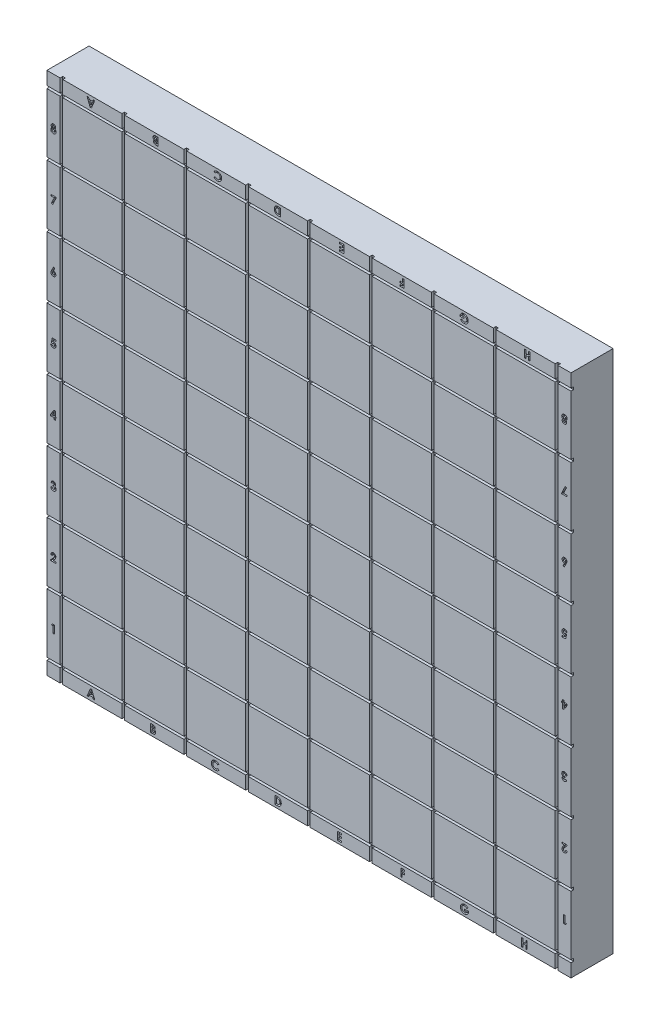
SolidWorks part; units mm, degrees
ref_plane "Płaszczyzna przednia" through (0, 0, 0) normal (0, 0, 1) x (1, 0, 0)
ref_plane "Płaszczyzna górna" through (0, 0, 0) normal (0, 1, 0) x (1, 0, 0)
ref_plane "Płaszczyzna prawa" through (0, 0, 0) normal (1, 0, 0) x (0, 0, -1)
sketch "Szkic3" plane through (0, 0, 0) normal (0, 0, 1) x (1, 0, 0)
  line L0 (247.5956, 2770.7602) -> (247.5956, 2725.7602)
  line L1 (200.5956, 2770.7602) -> (245.5956, 2770.7602)
  line L2 (200.5956, 2770.7602) -> (200.5956, 2725.7602)
  line L3 (200.5956, 2725.7602) -> (245.5956, 2725.7602)
  line L4 (245.5956, 2770.7602) -> (245.5956, 2725.7602)
  line L5 (247.5956, 2770.7602) -> (292.5956, 2770.7602)
  line L6 (292.5956, 2770.7602) -> (292.5956, 2725.7602)
  line L7 (247.5956, 2725.7602) -> (292.5956, 2725.7602)
  line L8 (294.5956, 2770.7602) -> (294.5956, 2725.7602)
  line L9 (294.5956, 2770.7602) -> (339.5956, 2770.7602)
  line L10 (339.5956, 2770.7602) -> (339.5956, 2725.7602)
  line L11 (294.5956, 2725.7602) -> (339.5956, 2725.7602)
  line L12 (341.5956, 2770.7602) -> (341.5956, 2725.7602)
  line L13 (341.5956, 2770.7602) -> (386.5956, 2770.7602)
  line L14 (386.5956, 2770.7602) -> (386.5956, 2725.7602)
  line L15 (341.5956, 2725.7602) -> (386.5956, 2725.7602)
  line L16 (388.5956, 2770.7602) -> (388.5956, 2725.7602)
  line L17 (388.5956, 2770.7602) -> (433.5956, 2770.7602)
  line L18 (433.5956, 2770.7602) -> (433.5956, 2725.7602)
  line L19 (388.5956, 2725.7602) -> (433.5956, 2725.7602)
  line L20 (435.5956, 2770.7602) -> (435.5956, 2725.7602)
  line L21 (435.5956, 2770.7602) -> (480.5956, 2770.7602)
  line L22 (480.5956, 2770.7602) -> (480.5956, 2725.7602)
  line L23 (435.5956, 2725.7602) -> (480.5956, 2725.7602)
  line L24 (482.5956, 2770.7602) -> (482.5956, 2725.7602)
  line L25 (482.5956, 2770.7602) -> (527.5956, 2770.7602)
  line L26 (527.5956, 2770.7602) -> (527.5956, 2725.7602)
  line L27 (482.5956, 2725.7602) -> (527.5956, 2725.7602)
  line L28 (529.5956, 2770.7602) -> (529.5956, 2725.7602)
  line L29 (529.5956, 2770.7602) -> (574.5956, 2770.7602)
  line L30 (574.5956, 2770.7602) -> (574.5956, 2725.7602)
  line L31 (529.5956, 2725.7602) -> (574.5956, 2725.7602)
  line L32 (247.5956, 2723.7602) -> (247.5956, 2678.7602)
  line L33 (247.5956, 2723.7602) -> (292.5956, 2723.7602)
  line L34 (292.5956, 2723.7602) -> (292.5956, 2678.7602)
  line L35 (247.5956, 2678.7602) -> (292.5956, 2678.7602)
  line L36 (294.5956, 2723.7602) -> (294.5956, 2678.7602)
  line L37 (294.5956, 2723.7602) -> (339.5956, 2723.7602)
  line L38 (339.5956, 2723.7602) -> (339.5956, 2678.7602)
  line L39 (294.5956, 2678.7602) -> (339.5956, 2678.7602)
  line L40 (341.5956, 2723.7602) -> (341.5956, 2678.7602)
  line L41 (341.5956, 2723.7602) -> (386.5956, 2723.7602)
  line L42 (386.5956, 2723.7602) -> (386.5956, 2678.7602)
  line L43 (341.5956, 2678.7602) -> (386.5956, 2678.7602)
  line L44 (388.5956, 2723.7602) -> (388.5956, 2678.7602)
  line L45 (388.5956, 2723.7602) -> (433.5956, 2723.7602)
  line L46 (433.5956, 2723.7602) -> (433.5956, 2678.7602)
  line L47 (388.5956, 2678.7602) -> (433.5956, 2678.7602)
  line L48 (435.5956, 2723.7602) -> (435.5956, 2678.7602)
  line L49 (435.5956, 2723.7602) -> (480.5956, 2723.7602)
  line L50 (480.5956, 2723.7602) -> (480.5956, 2678.7602)
  line L51 (435.5956, 2678.7602) -> (480.5956, 2678.7602)
  line L52 (482.5956, 2723.7602) -> (482.5956, 2678.7602)
  line L53 (482.5956, 2723.7602) -> (527.5956, 2723.7602)
  line L54 (527.5956, 2723.7602) -> (527.5956, 2678.7602)
  line L55 (482.5956, 2678.7602) -> (527.5956, 2678.7602)
  line L56 (529.5956, 2723.7602) -> (529.5956, 2678.7602)
  line L57 (529.5956, 2723.7602) -> (574.5956, 2723.7602)
  line L58 (574.5956, 2723.7602) -> (574.5956, 2678.7602)
  line L59 (529.5956, 2678.7602) -> (574.5956, 2678.7602)
  line L60 (247.5956, 2676.7602) -> (247.5956, 2631.7602)
  line L61 (247.5956, 2676.7602) -> (292.5956, 2676.7602)
  line L62 (292.5956, 2676.7602) -> (292.5956, 2631.7602)
  line L63 (247.5956, 2631.7602) -> (292.5956, 2631.7602)
  line L64 (294.5956, 2676.7602) -> (294.5956, 2631.7602)
  line L65 (294.5956, 2676.7602) -> (339.5956, 2676.7602)
  line L66 (339.5956, 2676.7602) -> (339.5956, 2631.7602)
  line L67 (294.5956, 2631.7602) -> (339.5956, 2631.7602)
  line L68 (341.5956, 2676.7602) -> (341.5956, 2631.7602)
  line L69 (341.5956, 2676.7602) -> (386.5956, 2676.7602)
  line L70 (386.5956, 2676.7602) -> (386.5956, 2631.7602)
  line L71 (341.5956, 2631.7602) -> (386.5956, 2631.7602)
  line L72 (388.5956, 2676.7602) -> (388.5956, 2631.7602)
  line L73 (388.5956, 2676.7602) -> (433.5956, 2676.7602)
  line L74 (433.5956, 2676.7602) -> (433.5956, 2631.7602)
  line L75 (388.5956, 2631.7602) -> (433.5956, 2631.7602)
  line L76 (435.5956, 2676.7602) -> (435.5956, 2631.7602)
  line L77 (435.5956, 2676.7602) -> (480.5956, 2676.7602)
  line L78 (480.5956, 2676.7602) -> (480.5956, 2631.7602)
  line L79 (435.5956, 2631.7602) -> (480.5956, 2631.7602)
  line L80 (482.5956, 2676.7602) -> (482.5956, 2631.7602)
  line L81 (482.5956, 2676.7602) -> (527.5956, 2676.7602)
  line L82 (527.5956, 2676.7602) -> (527.5956, 2631.7602)
  line L83 (482.5956, 2631.7602) -> (527.5956, 2631.7602)
  line L84 (529.5956, 2676.7602) -> (529.5956, 2631.7602)
  line L85 (529.5956, 2676.7602) -> (574.5956, 2676.7602)
  line L86 (574.5956, 2676.7602) -> (574.5956, 2631.7602)
  line L87 (529.5956, 2631.7602) -> (574.5956, 2631.7602)
  line L88 (247.5956, 2629.7602) -> (247.5956, 2584.7602)
  line L89 (247.5956, 2629.7602) -> (292.5956, 2629.7602)
  line L90 (292.5956, 2629.7602) -> (292.5956, 2584.7602)
  line L91 (247.5956, 2584.7602) -> (292.5956, 2584.7602)
  line L92 (294.5956, 2629.7602) -> (294.5956, 2584.7602)
  line L93 (294.5956, 2629.7602) -> (339.5956, 2629.7602)
  line L94 (339.5956, 2629.7602) -> (339.5956, 2584.7602)
  line L95 (294.5956, 2584.7602) -> (339.5956, 2584.7602)
  line L96 (341.5956, 2629.7602) -> (341.5956, 2584.7602)
  line L97 (341.5956, 2629.7602) -> (386.5956, 2629.7602)
  line L98 (386.5956, 2629.7602) -> (386.5956, 2584.7602)
  line L99 (341.5956, 2584.7602) -> (386.5956, 2584.7602)
  line L100 (388.5956, 2629.7602) -> (388.5956, 2584.7602)
  line L101 (388.5956, 2629.7602) -> (433.5956, 2629.7602)
  line L102 (433.5956, 2629.7602) -> (433.5956, 2584.7602)
  line L103 (388.5956, 2584.7602) -> (433.5956, 2584.7602)
  line L104 (435.5956, 2629.7602) -> (435.5956, 2584.7602)
  line L105 (435.5956, 2629.7602) -> (480.5956, 2629.7602)
  line L106 (480.5956, 2629.7602) -> (480.5956, 2584.7602)
  line L107 (435.5956, 2584.7602) -> (480.5956, 2584.7602)
  line L108 (482.5956, 2629.7602) -> (482.5956, 2584.7602)
  line L109 (482.5956, 2629.7602) -> (527.5956, 2629.7602)
  line L110 (527.5956, 2629.7602) -> (527.5956, 2584.7602)
  line L111 (482.5956, 2584.7602) -> (527.5956, 2584.7602)
  line L112 (529.5956, 2629.7602) -> (529.5956, 2584.7602)
  line L113 (529.5956, 2629.7602) -> (574.5956, 2629.7602)
  line L114 (574.5956, 2629.7602) -> (574.5956, 2584.7602)
  line L115 (529.5956, 2584.7602) -> (574.5956, 2584.7602)
  line L116 (247.5956, 2582.7602) -> (247.5956, 2537.7602)
  line L117 (247.5956, 2582.7602) -> (292.5956, 2582.7602)
  line L118 (292.5956, 2582.7602) -> (292.5956, 2537.7602)
  line L119 (247.5956, 2537.7602) -> (292.5956, 2537.7602)
  line L120 (294.5956, 2582.7602) -> (294.5956, 2537.7602)
  line L121 (294.5956, 2582.7602) -> (339.5956, 2582.7602)
  line L122 (339.5956, 2582.7602) -> (339.5956, 2537.7602)
  line L123 (294.5956, 2537.7602) -> (339.5956, 2537.7602)
  line L124 (341.5956, 2582.7602) -> (341.5956, 2537.7602)
  line L125 (341.5956, 2582.7602) -> (386.5956, 2582.7602)
  line L126 (386.5956, 2582.7602) -> (386.5956, 2537.7602)
  line L127 (341.5956, 2537.7602) -> (386.5956, 2537.7602)
  line L128 (388.5956, 2582.7602) -> (388.5956, 2537.7602)
  line L129 (388.5956, 2582.7602) -> (433.5956, 2582.7602)
  line L130 (433.5956, 2582.7602) -> (433.5956, 2537.7602)
  line L131 (388.5956, 2537.7602) -> (433.5956, 2537.7602)
  line L132 (435.5956, 2582.7602) -> (435.5956, 2537.7602)
  line L133 (435.5956, 2582.7602) -> (480.5956, 2582.7602)
  line L134 (480.5956, 2582.7602) -> (480.5956, 2537.7602)
  line L135 (435.5956, 2537.7602) -> (480.5956, 2537.7602)
  line L136 (482.5956, 2582.7602) -> (482.5956, 2537.7602)
  line L137 (482.5956, 2582.7602) -> (527.5956, 2582.7602)
  line L138 (527.5956, 2582.7602) -> (527.5956, 2537.7602)
  line L139 (482.5956, 2537.7602) -> (527.5956, 2537.7602)
  line L140 (529.5956, 2582.7602) -> (529.5956, 2537.7602)
  line L141 (529.5956, 2582.7602) -> (574.5956, 2582.7602)
  line L142 (574.5956, 2582.7602) -> (574.5956, 2537.7602)
  line L143 (529.5956, 2537.7602) -> (574.5956, 2537.7602)
  line L144 (247.5956, 2535.7602) -> (247.5956, 2490.7602)
  line L145 (247.5956, 2535.7602) -> (292.5956, 2535.7602)
  line L146 (292.5956, 2535.7602) -> (292.5956, 2490.7602)
  line L147 (247.5956, 2490.7602) -> (292.5956, 2490.7602)
  line L148 (294.5956, 2535.7602) -> (294.5956, 2490.7602)
  line L149 (294.5956, 2535.7602) -> (339.5956, 2535.7602)
  line L150 (339.5956, 2535.7602) -> (339.5956, 2490.7602)
  line L151 (294.5956, 2490.7602) -> (339.5956, 2490.7602)
  line L152 (341.5956, 2535.7602) -> (341.5956, 2490.7602)
  line L153 (341.5956, 2535.7602) -> (386.5956, 2535.7602)
  line L154 (386.5956, 2535.7602) -> (386.5956, 2490.7602)
  line L155 (341.5956, 2490.7602) -> (386.5956, 2490.7602)
  line L156 (388.5956, 2535.7602) -> (388.5956, 2490.7602)
  line L157 (388.5956, 2535.7602) -> (433.5956, 2535.7602)
  line L158 (433.5956, 2535.7602) -> (433.5956, 2490.7602)
  line L159 (388.5956, 2490.7602) -> (433.5956, 2490.7602)
  line L160 (435.5956, 2535.7602) -> (435.5956, 2490.7602)
  line L161 (435.5956, 2535.7602) -> (480.5956, 2535.7602)
  line L162 (480.5956, 2535.7602) -> (480.5956, 2490.7602)
  line L163 (435.5956, 2490.7602) -> (480.5956, 2490.7602)
  line L164 (482.5956, 2535.7602) -> (482.5956, 2490.7602)
  line L165 (482.5956, 2535.7602) -> (527.5956, 2535.7602)
  line L166 (527.5956, 2535.7602) -> (527.5956, 2490.7602)
  line L167 (482.5956, 2490.7602) -> (527.5956, 2490.7602)
  line L168 (529.5956, 2535.7602) -> (529.5956, 2490.7602)
  line L169 (529.5956, 2535.7602) -> (574.5956, 2535.7602)
  line L170 (574.5956, 2535.7602) -> (574.5956, 2490.7602)
  line L171 (529.5956, 2490.7602) -> (574.5956, 2490.7602)
  line L172 (247.5956, 2488.7602) -> (247.5956, 2443.7602)
  line L173 (247.5956, 2488.7602) -> (292.5956, 2488.7602)
  line L174 (292.5956, 2488.7602) -> (292.5956, 2443.7602)
  line L175 (247.5956, 2443.7602) -> (292.5956, 2443.7602)
  line L176 (294.5956, 2488.7602) -> (294.5956, 2443.7602)
  line L177 (294.5956, 2488.7602) -> (339.5956, 2488.7602)
  line L178 (339.5956, 2488.7602) -> (339.5956, 2443.7602)
  line L179 (294.5956, 2443.7602) -> (339.5956, 2443.7602)
  line L180 (341.5956, 2488.7602) -> (341.5956, 2443.7602)
  line L181 (341.5956, 2488.7602) -> (386.5956, 2488.7602)
  line L182 (386.5956, 2488.7602) -> (386.5956, 2443.7602)
  line L183 (341.5956, 2443.7602) -> (386.5956, 2443.7602)
  line L184 (388.5956, 2488.7602) -> (388.5956, 2443.7602)
  line L185 (388.5956, 2488.7602) -> (433.5956, 2488.7602)
  line L186 (433.5956, 2488.7602) -> (433.5956, 2443.7602)
  line L187 (388.5956, 2443.7602) -> (433.5956, 2443.7602)
  line L188 (435.5956, 2488.7602) -> (435.5956, 2443.7602)
  line L189 (435.5956, 2488.7602) -> (480.5956, 2488.7602)
  line L190 (480.5956, 2488.7602) -> (480.5956, 2443.7602)
  line L191 (435.5956, 2443.7602) -> (480.5956, 2443.7602)
  line L192 (482.5956, 2488.7602) -> (482.5956, 2443.7602)
  line L193 (482.5956, 2488.7602) -> (527.5956, 2488.7602)
  line L194 (527.5956, 2488.7602) -> (527.5956, 2443.7602)
  line L195 (482.5956, 2443.7602) -> (527.5956, 2443.7602)
  line L196 (529.5956, 2488.7602) -> (529.5956, 2443.7602)
  line L197 (529.5956, 2488.7602) -> (574.5956, 2488.7602)
  line L198 (574.5956, 2488.7602) -> (574.5956, 2443.7602)
  line L199 (529.5956, 2443.7602) -> (574.5956, 2443.7602)
  line L200 (247.5956, 2441.7602) -> (247.5956, 2396.7602)
  line L201 (247.5956, 2441.7602) -> (292.5956, 2441.7602)
  line L202 (292.5956, 2441.7602) -> (292.5956, 2396.7602)
  line L203 (247.5956, 2396.7602) -> (292.5956, 2396.7602)
  line L204 (294.5956, 2441.7602) -> (294.5956, 2396.7602)
  line L205 (294.5956, 2441.7602) -> (339.5956, 2441.7602)
  line L206 (339.5956, 2441.7602) -> (339.5956, 2396.7602)
  line L207 (294.5956, 2396.7602) -> (339.5956, 2396.7602)
  line L208 (341.5956, 2441.7602) -> (341.5956, 2396.7602)
  line L209 (341.5956, 2441.7602) -> (386.5956, 2441.7602)
  line L210 (386.5956, 2441.7602) -> (386.5956, 2396.7602)
  line L211 (341.5956, 2396.7602) -> (386.5956, 2396.7602)
  line L212 (388.5956, 2441.7602) -> (388.5956, 2396.7602)
  line L213 (388.5956, 2441.7602) -> (433.5956, 2441.7602)
  line L214 (433.5956, 2441.7602) -> (433.5956, 2396.7602)
  line L215 (388.5956, 2396.7602) -> (433.5956, 2396.7602)
  line L216 (435.5956, 2441.7602) -> (435.5956, 2396.7602)
  line L217 (435.5956, 2441.7602) -> (480.5956, 2441.7602)
  line L218 (480.5956, 2441.7602) -> (480.5956, 2396.7602)
  line L219 (435.5956, 2396.7602) -> (480.5956, 2396.7602)
  line L220 (482.5956, 2441.7602) -> (482.5956, 2396.7602)
  line L221 (482.5956, 2441.7602) -> (527.5956, 2441.7602)
  line L222 (527.5956, 2441.7602) -> (527.5956, 2396.7602)
  line L223 (482.5956, 2396.7602) -> (527.5956, 2396.7602)
  line L224 (529.5956, 2441.7602) -> (529.5956, 2396.7602)
  line L225 (529.5956, 2441.7602) -> (574.5956, 2441.7602)
  line L226 (574.5956, 2441.7602) -> (574.5956, 2396.7602)
  line L227 (529.5956, 2396.7602) -> (574.5956, 2396.7602)
  line L228 (200.5956, 2723.7602) -> (200.5956, 2678.7602)
  line L229 (200.5956, 2723.7602) -> (245.5956, 2723.7602)
  line L230 (245.5956, 2723.7602) -> (245.5956, 2678.7602)
  line L231 (200.5956, 2678.7602) -> (245.5956, 2678.7602)
  line L232 (200.5956, 2676.7602) -> (200.5956, 2631.7602)
  line L233 (200.5956, 2676.7602) -> (245.5956, 2676.7602)
  line L234 (245.5956, 2676.7602) -> (245.5956, 2631.7602)
  line L235 (200.5956, 2631.7602) -> (245.5956, 2631.7602)
  line L236 (200.5956, 2629.7602) -> (200.5956, 2584.7602)
  line L237 (200.5956, 2629.7602) -> (245.5956, 2629.7602)
  line L238 (245.5956, 2629.7602) -> (245.5956, 2584.7602)
  line L239 (200.5956, 2584.7602) -> (245.5956, 2584.7602)
  line L240 (200.5956, 2582.7602) -> (200.5956, 2537.7602)
  line L241 (200.5956, 2582.7602) -> (245.5956, 2582.7602)
  line L242 (245.5956, 2582.7602) -> (245.5956, 2537.7602)
  line L243 (200.5956, 2537.7602) -> (245.5956, 2537.7602)
  line L244 (200.5956, 2535.7602) -> (200.5956, 2490.7602)
  line L245 (200.5956, 2535.7602) -> (245.5956, 2535.7602)
  line L246 (245.5956, 2535.7602) -> (245.5956, 2490.7602)
  line L247 (200.5956, 2490.7602) -> (245.5956, 2490.7602)
  line L248 (200.5956, 2488.7602) -> (200.5956, 2443.7602)
  line L249 (200.5956, 2488.7602) -> (245.5956, 2488.7602)
  line L250 (245.5956, 2488.7602) -> (245.5956, 2443.7602)
  line L251 (200.5956, 2443.7602) -> (245.5956, 2443.7602)
  line L252 (200.5956, 2441.7602) -> (200.5956, 2396.7602)
  line L253 (200.5956, 2441.7602) -> (245.5956, 2441.7602)
  line L254 (245.5956, 2441.7602) -> (245.5956, 2396.7602)
  line L255 (200.5956, 2396.7602) -> (245.5956, 2396.7602)
  line L258 (200.5956, 2772.7602) -> (245.5956, 2772.7602)
  line L259 (198.5956, 2772.7602) -> (188.5956, 2772.7602)
  line L260 (198.5956, 2772.7602) -> (198.5956, 2782.7602)
  line L261 (198.5956, 2782.7602) -> (188.5956, 2782.7602)
  line L262 (188.5956, 2772.7602) -> (188.5956, 2782.7602)
  line L263 (245.5956, 2772.7602) -> (245.5956, 2782.7602)
  line L264 (245.5956, 2782.7602) -> (200.5956, 2782.7602)
  line L265 (200.5956, 2782.7602) -> (200.5956, 2772.7602)
  line L266 (198.5956, 2770.7602) -> (198.5956, 2725.7602)
  line L267 (198.5956, 2725.7602) -> (188.5956, 2725.7602)
  line L268 (188.5956, 2725.7602) -> (188.5956, 2770.7602)
  line L269 (188.5956, 2770.7602) -> (198.5956, 2770.7602)
  line L270 (247.5956, 2782.7602) -> (247.5956, 2772.7602)
  line L271 (247.5956, 2772.7602) -> (292.5956, 2772.7602)
  line L272 (292.5956, 2772.7602) -> (292.5956, 2782.7602)
  line L273 (292.5956, 2782.7602) -> (247.5956, 2782.7602)
  line L274 (294.5956, 2782.7602) -> (294.5956, 2772.7602)
  line L275 (294.5956, 2772.7602) -> (339.5956, 2772.7602)
  line L276 (339.5956, 2772.7602) -> (339.5956, 2782.7602)
  line L277 (339.5956, 2782.7602) -> (294.5956, 2782.7602)
  line L278 (341.5956, 2782.7602) -> (341.5956, 2772.7602)
  line L279 (341.5956, 2772.7602) -> (386.5956, 2772.7602)
  line L280 (386.5956, 2772.7602) -> (386.5956, 2782.7602)
  line L281 (386.5956, 2782.7602) -> (341.5956, 2782.7602)
  line L282 (388.5956, 2782.7602) -> (388.5956, 2772.7602)
  line L283 (388.5956, 2772.7602) -> (433.5956, 2772.7602)
  line L284 (433.5956, 2772.7602) -> (433.5956, 2782.7602)
  line L285 (433.5956, 2782.7602) -> (388.5956, 2782.7602)
  line L286 (435.5956, 2782.7602) -> (435.5956, 2772.7602)
  line L287 (435.5956, 2772.7602) -> (480.5956, 2772.7602)
  line L288 (480.5956, 2772.7602) -> (480.5956, 2782.7602)
  line L289 (480.5956, 2782.7602) -> (435.5956, 2782.7602)
  line L290 (482.5956, 2782.7602) -> (482.5956, 2772.7602)
  line L291 (482.5956, 2772.7602) -> (527.5956, 2772.7602)
  line L292 (527.5956, 2772.7602) -> (527.5956, 2782.7602)
  line L293 (527.5956, 2782.7602) -> (482.5956, 2782.7602)
  line L294 (529.5956, 2782.7602) -> (529.5956, 2772.7602)
  line L295 (529.5956, 2772.7602) -> (574.5956, 2772.7602)
  line L296 (574.5956, 2772.7602) -> (574.5956, 2782.7602)
  line L297 (574.5956, 2782.7602) -> (529.5956, 2782.7602)
  line L298 (247.5956, 2394.7602) -> (247.5956, 2384.7602)
  line L299 (247.5956, 2384.7602) -> (292.5956, 2384.7602)
  line L300 (292.5956, 2384.7602) -> (292.5956, 2394.7602)
  line L301 (292.5956, 2394.7602) -> (247.5956, 2394.7602)
  line L302 (294.5956, 2394.7602) -> (294.5956, 2384.7602)
  line L303 (294.5956, 2384.7602) -> (339.5956, 2384.7602)
  line L304 (339.5956, 2384.7602) -> (339.5956, 2394.7602)
  line L305 (339.5956, 2394.7602) -> (294.5956, 2394.7602)
  line L306 (341.5956, 2394.7602) -> (341.5956, 2384.7602)
  line L307 (341.5956, 2384.7602) -> (386.5956, 2384.7602)
  line L308 (386.5956, 2384.7602) -> (386.5956, 2394.7602)
  line L309 (386.5956, 2394.7602) -> (341.5956, 2394.7602)
  line L310 (388.5956, 2394.7602) -> (388.5956, 2384.7602)
  line L311 (388.5956, 2384.7602) -> (433.5956, 2384.7602)
  line L312 (433.5956, 2384.7602) -> (433.5956, 2394.7602)
  line L313 (433.5956, 2394.7602) -> (388.5956, 2394.7602)
  line L314 (435.5956, 2394.7602) -> (435.5956, 2384.7602)
  line L315 (435.5956, 2384.7602) -> (480.5956, 2384.7602)
  line L316 (480.5956, 2384.7602) -> (480.5956, 2394.7602)
  line L317 (480.5956, 2394.7602) -> (435.5956, 2394.7602)
  line L318 (482.5956, 2394.7602) -> (482.5956, 2384.7602)
  line L319 (482.5956, 2384.7602) -> (527.5956, 2384.7602)
  line L320 (527.5956, 2384.7602) -> (527.5956, 2394.7602)
  line L321 (527.5956, 2394.7602) -> (482.5956, 2394.7602)
  line L322 (529.5956, 2394.7602) -> (529.5956, 2384.7602)
  line L323 (529.5956, 2384.7602) -> (574.5956, 2384.7602)
  line L324 (574.5956, 2384.7602) -> (574.5956, 2394.7602)
  line L325 (574.5956, 2394.7602) -> (529.5956, 2394.7602)
  line L326 (200.5956, 2394.7602) -> (200.5956, 2384.7602)
  line L327 (200.5956, 2384.7602) -> (245.5956, 2384.7602)
  line L328 (245.5956, 2384.7602) -> (245.5956, 2394.7602)
  line L329 (245.5956, 2394.7602) -> (200.5956, 2394.7602)
  line L330 (586.5956, 2770.7602) -> (586.5956, 2725.7602)
  line L331 (586.5956, 2725.7602) -> (576.5956, 2725.7602)
  line L332 (576.5956, 2725.7602) -> (576.5956, 2770.7602)
  line L333 (576.5956, 2770.7602) -> (586.5956, 2770.7602)
  line L334 (586.5956, 2723.7602) -> (586.5956, 2678.7602)
  line L335 (586.5956, 2678.7602) -> (576.5956, 2678.7602)
  line L336 (576.5956, 2678.7602) -> (576.5956, 2723.7602)
  line L337 (576.5956, 2723.7602) -> (586.5956, 2723.7602)
  line L338 (586.5956, 2676.7602) -> (586.5956, 2631.7602)
  line L339 (586.5956, 2631.7602) -> (576.5956, 2631.7602)
  line L340 (576.5956, 2631.7602) -> (576.5956, 2676.7602)
  line L341 (576.5956, 2676.7602) -> (586.5956, 2676.7602)
  line L342 (586.5956, 2629.7602) -> (586.5956, 2584.7602)
  line L343 (586.5956, 2584.7602) -> (576.5956, 2584.7602)
  line L344 (576.5956, 2584.7602) -> (576.5956, 2629.7602)
  line L345 (576.5956, 2629.7602) -> (586.5956, 2629.7602)
  line L346 (586.5956, 2582.7602) -> (586.5956, 2537.7602)
  line L347 (586.5956, 2537.7602) -> (576.5956, 2537.7602)
  line L348 (576.5956, 2537.7602) -> (576.5956, 2582.7602)
  line L349 (576.5956, 2582.7602) -> (586.5956, 2582.7602)
  line L350 (586.5956, 2535.7602) -> (586.5956, 2490.7602)
  line L351 (586.5956, 2490.7602) -> (576.5956, 2490.7602)
  line L352 (576.5956, 2490.7602) -> (576.5956, 2535.7602)
  line L353 (576.5956, 2535.7602) -> (586.5956, 2535.7602)
  line L354 (586.5956, 2488.7602) -> (586.5956, 2443.7602)
  line L355 (586.5956, 2443.7602) -> (576.5956, 2443.7602)
  line L356 (576.5956, 2443.7602) -> (576.5956, 2488.7602)
  line L357 (576.5956, 2488.7602) -> (586.5956, 2488.7602)
  line L358 (586.5956, 2441.7602) -> (586.5956, 2396.7602)
  line L359 (586.5956, 2396.7602) -> (576.5956, 2396.7602)
  line L360 (576.5956, 2396.7602) -> (576.5956, 2441.7602)
  line L361 (576.5956, 2441.7602) -> (586.5956, 2441.7602)
  line L362 (198.5956, 2723.7602) -> (198.5956, 2678.7602)
  line L363 (198.5956, 2678.7602) -> (188.5956, 2678.7602)
  line L364 (188.5956, 2678.7602) -> (188.5956, 2723.7602)
  line L365 (188.5956, 2723.7602) -> (198.5956, 2723.7602)
  line L366 (198.5956, 2676.7602) -> (198.5956, 2631.7602)
  line L367 (198.5956, 2631.7602) -> (188.5956, 2631.7602)
  line L368 (188.5956, 2631.7602) -> (188.5956, 2676.7602)
  line L369 (188.5956, 2676.7602) -> (198.5956, 2676.7602)
  line L370 (198.5956, 2629.7602) -> (198.5956, 2584.7602)
  line L371 (198.5956, 2584.7602) -> (188.5956, 2584.7602)
  line L372 (188.5956, 2584.7602) -> (188.5956, 2629.7602)
  line L373 (188.5956, 2629.7602) -> (198.5956, 2629.7602)
  line L374 (198.5956, 2582.7602) -> (198.5956, 2537.7602)
  line L375 (198.5956, 2537.7602) -> (188.5956, 2537.7602)
  line L376 (188.5956, 2537.7602) -> (188.5956, 2582.7602)
  line L377 (188.5956, 2582.7602) -> (198.5956, 2582.7602)
  line L378 (198.5956, 2535.7602) -> (198.5956, 2490.7602)
  line L379 (198.5956, 2490.7602) -> (188.5956, 2490.7602)
  line L380 (188.5956, 2490.7602) -> (188.5956, 2535.7602)
  line L381 (188.5956, 2535.7602) -> (198.5956, 2535.7602)
  line L382 (198.5956, 2488.7602) -> (198.5956, 2443.7602)
  line L383 (198.5956, 2443.7602) -> (188.5956, 2443.7602)
  line L384 (188.5956, 2443.7602) -> (188.5956, 2488.7602)
  line L385 (188.5956, 2488.7602) -> (198.5956, 2488.7602)
  line L386 (198.5956, 2441.7602) -> (198.5956, 2396.7602)
  line L387 (198.5956, 2396.7602) -> (188.5956, 2396.7602)
  line L388 (188.5956, 2396.7602) -> (188.5956, 2441.7602)
  line L389 (188.5956, 2441.7602) -> (198.5956, 2441.7602)
  line L390 (586.5956, 2772.7602) -> (586.5956, 2782.7602)
  line L391 (586.5956, 2772.7602) -> (576.5956, 2772.7602)
  line L392 (576.5956, 2772.7602) -> (576.5956, 2782.7602)
  line L393 (586.5956, 2782.7602) -> (576.5956, 2782.7602)
  line L394 (586.5956, 2384.7602) -> (586.5956, 2394.7602)
  line L395 (586.5956, 2384.7602) -> (576.5956, 2384.7602)
  line L396 (576.5956, 2384.7602) -> (576.5956, 2394.7602)
  line L397 (586.5956, 2394.7602) -> (576.5956, 2394.7602)
  line L398 (198.5956, 2384.7602) -> (198.5956, 2394.7602)
  line L399 (198.5956, 2384.7602) -> (188.5956, 2384.7602)
  line L400 (188.5956, 2384.7602) -> (188.5956, 2394.7602)
  line L401 (198.5956, 2394.7602) -> (188.5956, 2394.7602)
  dimension "D2" = 45
  dimension "D6" = 2
  dimension "D7" = 10
  dimension "D8" = 10
  dimension "D3" = 8
  dimension "D4" = 8
  dimension "D9" = 8
  dimension "D10" = 2
  dimension "D11" = 2
  dimension "D12" = 8
  dimension "D13" = 2
  dimension "D14" = 2
extrude "Dodanie-wyciągnięcie3" add sketch "Szkic3" against normal blind 2
sketch "Szkic4" plane through (0, 0, -2) normal (0, 0, -1) x (-1, 0, 0)
  line L1 (-586.5956, 2782.7602) -> (-188.5956, 2782.7602)
  line L2 (-586.5956, 2782.7602) -> (-586.5956, 2384.7602)
  line L3 (-586.5956, 2384.7602) -> (-188.5956, 2384.7602)
  line L4 (-188.5956, 2782.7602) -> (-188.5956, 2384.7602)
extrude "Dodanie-wyciągnięcie4" add sketch "Szkic4" along normal blind 30
shell "Skorupa1" thickness 4 removed face at (387.5956, 2583.7602, -32)
sketch "Szkic5" plane through (0, 0, -6) normal (0, 0, -1) x (-1, 0, 0)
  line L1 (-586.5956, 2384.7602) -> (-188.5956, 2384.7602) construction
  line L2 (-192.5956, 2778.7602) -> (-582.5956, 2778.7602) construction
  line L8 (-582.5956, 2388.7602) -> (-192.5956, 2388.7602) construction
  line L14 (-582.5956, 2388.7602) -> (-192.5956, 2388.7602) construction
  line L17 (-372.5956, 2388.7602) -> (-402.5956, 2388.7602)
  line L21 (-402.5956, 2603.7602) -> (-582.5956, 2603.7602)
  line L22 (-582.5956, 2588.7602) -> (-582.5956, 2625.7602) construction
  line L25 (-582.5956, 2778.7602) -> (-582.5956, 2388.7602) construction
  line L27 (-192.5956, 2578.7602) -> (-192.5956, 2541.7602) construction
  line L28 (-192.5956, 2563.7602) -> (-192.5956, 2603.7602)
  line L29 (-192.5956, 2388.7602) -> (-192.5956, 2778.7602) construction
  line L30 (-192.5956, 2603.7602) -> (-372.5956, 2603.7602)
  line L31 (-402.5956, 2603.7602) -> (-402.5956, 2778.7602)
  line L32 (-372.5956, 2603.7602) -> (-372.5956, 2778.7602)
  line L33 (-402.5956, 2388.7602) -> (-402.5956, 2563.7602)
  line L34 (-402.5956, 2563.7602) -> (-582.5956, 2563.7602)
  line L35 (-372.5956, 2388.7602) -> (-372.5956, 2563.7602)
  line L36 (-372.5956, 2563.7602) -> (-192.5956, 2563.7602)
  line L37 (-582.5956, 2563.7602) -> (-582.5956, 2603.7602)
  line L39 (-188.5956, 2384.7602) -> (-188.5956, 2782.7602) construction
  line L40 (-402.5956, 2778.7602) -> (-372.5956, 2778.7602)
  dimension "D2" = 30
  dimension "D3" = 40
  dimension "D4" = 179
  dimension "D5" = 179
  dimension "D6" = 40
  dimension "D7" = 184
  dimension "D8" = 184
extrude "Dodanie-wyciągnięcie5" add sketch "Szkic5" along normal blind 26
sketch "Szkic6" plane through (582.5956, 0, 0) normal (-1, 0, 0) x (0, 0, 1)
  line L6 (-2, 2772.7602) -> (-2, 2782.7602)
  line L7 (-2, 2782.7602) -> (-6, 2782.7602)
  line L8 (-32, 2782.7602) -> (0, 2782.7602) construction
  line L9 (-6, 2782.7602) -> (-6, 2384.7602)
  line L10 (-32, 2384.7602) -> (0, 2384.7602) construction
  line L11 (-6, 2384.7602) -> (-2, 2384.7602)
  line L12 (-2, 2384.7602) -> (-2, 2772.7602)
  dimension "D1" = 4
extrude "Dodanie-wyciągnięcie7" add sketch "Szkic6" along normal blind 390 contours L9 L11 L12 L6 L7
sketch "Szkic7" plane through (0, 0, 0) normal (0, 0, 1) x (1, 0, 0)
  text T0 "<b>        A                  B                  C                  D                  E                   F                  G                 H </b>" font "Century Gothic" height 6
  text T1 "<b>8</b>\r\n"
  text T2 "<b>7</b>"
  text T3 "<b>6</b>"
  text T4 "<b>5</b>"
  text T5 "<b>4</b>"
  text T6 "<b>3</b>"
  text T7 "<b>2</b>"
  text T8 "<b>1</b>"
  text T9 "<b>8</b>"
  text T10 "<b>7</b>"
  text T11 "<b>6</b>"
  text T12 "<b>5</b>"
  text T13 "<b>4</b>"
  text T14 "<b>3</b>"
  text T15 "<b>2</b>"
  text T16 "<b>1</b>"
  text T17 "<b>        H                  G                  F                  E                   D                 C                  B                   A</b>"
  dimension "D3" = 1
extrude "Wytnij-wyciągnięcie2" cut sketch "Szkic7" against normal blind 2
ref_plane "Płaszczyzna1" through (0, 2583.7602, 0) normal (0, 1, 0) x (1, 0, 0)
sketch "Szkic9" plane through (0, 2583.7602, 0) normal (0, 1, 0) x (1, 0, 0)
  line L0 (188.5956, 0) -> (188.5956, 32)
  line L1 (188.5956, 32) -> (586.5956, 32)
  line L2 (586.5956, 32) -> (586.5956, 0)
  line L3 (586.5956, 0) -> (576.5956, 0) construction
  line L4 (586.5956, 32) -> (586.5956, 0) construction
  line L5 (586.5956, 0) -> (188.5956, 0)
sketch "Szkic10" plane through (0, 0, -32) normal (0, 0, -1) x (-1, 0, 0)
  line L0 (-402.5956, 2603.7602) -> (-582.5956, 2603.7602) construction
  line L1 (-516.5956, 2603.7602) -> (-476.5956, 2603.7602)
  line L2 (-516.5956, 2603.7602) -> (-516.5956, 2563.7602)
  line L3 (-516.5956, 2563.7602) -> (-476.5956, 2563.7602)
  line L4 (-476.5956, 2603.7602) -> (-476.5956, 2563.7602)
  line L5 (-582.5956, 2563.7602) -> (-402.5956, 2563.7602) construction
  line L6 (-586.5956, 2782.7602) -> (-586.5956, 2384.7602) construction
  line L7 (-372.5956, 2563.7602) -> (-192.5956, 2563.7602) construction
  line L8 (-298.5956, 2563.7602) -> (-258.5956, 2563.7602)
  line L9 (-298.5956, 2563.7602) -> (-298.5956, 2603.7602)
  line L10 (-298.5956, 2603.7602) -> (-258.5956, 2603.7602)
  line L11 (-258.5956, 2563.7602) -> (-258.5956, 2603.7602)
  line L12 (-192.5956, 2603.7602) -> (-372.5956, 2603.7602) construction
  line L13 (-188.5956, 2384.7602) -> (-188.5956, 2782.7602) construction
  dimension "D1" = 40
  dimension "D2" = 70
  dimension "D3" = 40
  dimension "D4" = 70
extrude "Wytnij-wyciągnięcie4" cut sketch "Szkic10" against normal blind 1
sketch "Szkic11" plane through (0, 0, -31) normal (0, 0, -1) x (-1, 0, 0)
  line L0 (249.3333, 1000) -> (1246.6667, 1000) construction
  line L1 (15.6407, 3558.0244) -> (1012.936, 3566.7277) construction
sketch "Szkic12" plane through (0, 0, -31) normal (0, 0, -1) x (-1, 0, 0)
  circle A0 centre (-291.8238, 2597.8141) radius 1.1765
  circle A1 centre (-278.6495, 2594.3851) radius 1.6785
  circle A2 centre (-265.2046, 2597.8141) radius 1.3414
  circle A3 centre (-278.6495, 2574.2629) radius 1.7239
  circle A4 centre (-291.8238, 2570.3828) radius 1.4936
  circle A5 centre (-265.2046, 2570.3828) radius 1.0866
